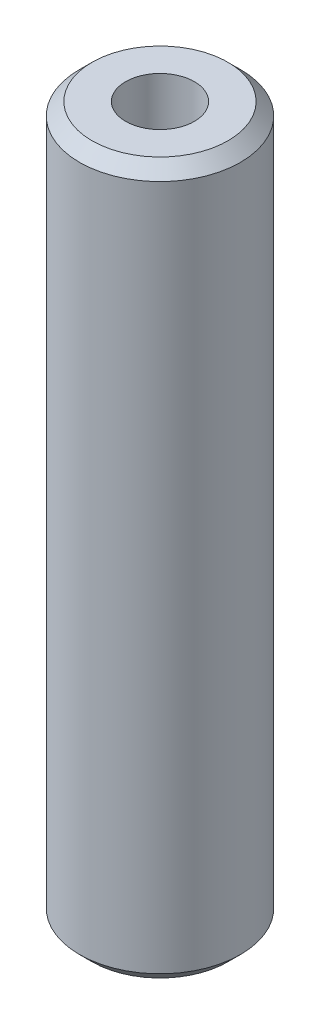
SolidWorks part; units mm, degrees
ref_plane "Front Plane" through (0, 0, 0) normal (0, 0, 1) x (1, 0, 0)
ref_plane "Top Plane" through (0, 0, 0) normal (0, 1, 0) x (1, 0, 0)
ref_plane "Right Plane" through (0, 0, 0) normal (1, 0, 0) x (0, 0, -1)
sketch "Sketch1" plane through (0, 0, 0) normal (0, 1, 0) x (1, 0, 0)
  circle A0 centre (0, 0) radius 37.5
  dimension "SHAFT_OD" = 75
extrude "Boss-Extrude1" add sketch "Sketch1" along normal blind 331.3317
sketch "Sketch2" plane through (0, 0, 0) normal (0, 1, 0) x (1, 0, 0)
  circle A0 centre (0, 0) radius 16.0362
  dimension "BORE_D" = 32.0723
extrude "Cut-Extrude1" cut sketch "Sketch2" along normal through all
chamfer "Chamfer1" distance 5.8126 angle 45 2 edges at (0, 331.3317, 37.5) (0, 0, 37.5)
